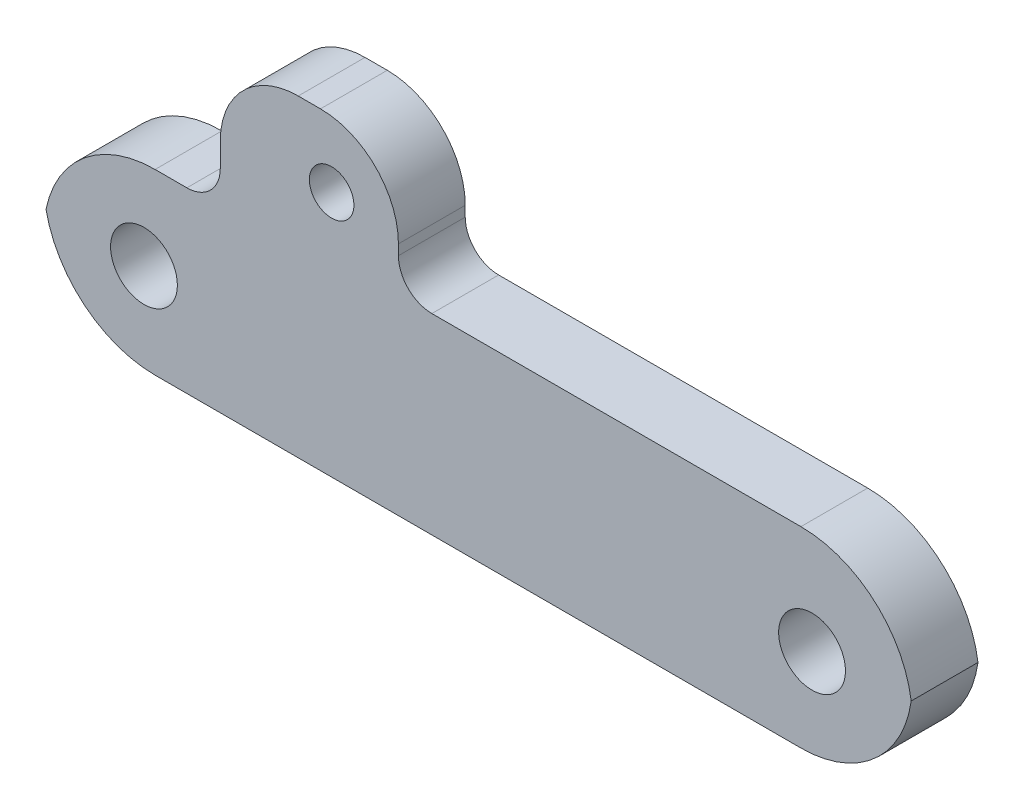
SolidWorks part; units mm, degrees
ref_plane "Front" through (0, 0, 0) normal (0, 0, 1) x (1, 0, 0)
ref_plane "Top" through (0, 0, 0) normal (0, 1, 0) x (1, 0, 0)
ref_plane "Right" through (0, 0, 0) normal (1, 0, 0) x (0, 0, -1)
sketch "Sketch1" plane through (0, 0, 0) normal (0, 0, 1) x (1, 0, 0)
  line L0 (4.5, 4) -> (12.9265, 11.0707) construction
  line L1 (0, 0) -> (39, 0)
  line L2 (0, 0) -> (0, 8)
  line L4 (39, 0) -> (39, 8.6106)
  line L9 (4.5, 4) -> (10.9564, 4) construction
  line L10 (15.9265, 8.6106) -> (39, 8.6106)
  line L13 (7.9265, 14.0707) -> (15.9265, 14.0707)
  line L14 (15.9265, 8.6106) -> (15.9265, 14.0707)
  line L15 (0, 8) -> (7.9265, 8)
  line L16 (7.9265, 8) -> (7.9265, 14.0707)
  circle A0 centre (4.5, 4) radius 1.5
  circle A1 centre (34.5, 4) radius 1.5
  circle A2 centre (12.9265, 11.0707) radius 1
  dimension "D3" = 3
  dimension "D4" = 3
  dimension "D5" = 3
  dimension "D9" = 2
  dimension "D10" = 2
  dimension "D11" = 4
  dimension "D12" = 2
  dimension "D1" = 8
  dimension "D2" = 30
  dimension "D6" = 3
  dimension "D7" = 11
  dimension "D8" = 40
extrude "Boss-Extrude1" add sketch "Sketch1" along normal blind 3
fillet "Fillet1" radius 5 4 edges at (39, 8.6106, 1.5) (39, 0, 1.5) (0, 0, 1.5) (0, 8, 1.5)
fillet "Fillet2" radius 3.5 2 edges at (15.9265, 14.0707, 1.5) (7.9265, 14.0707, 1.5)
fillet "Fillet3" radius 1.5 2 edges at (7.9265, 8, 1.5) (15.9265, 8.6106, 1.5)
